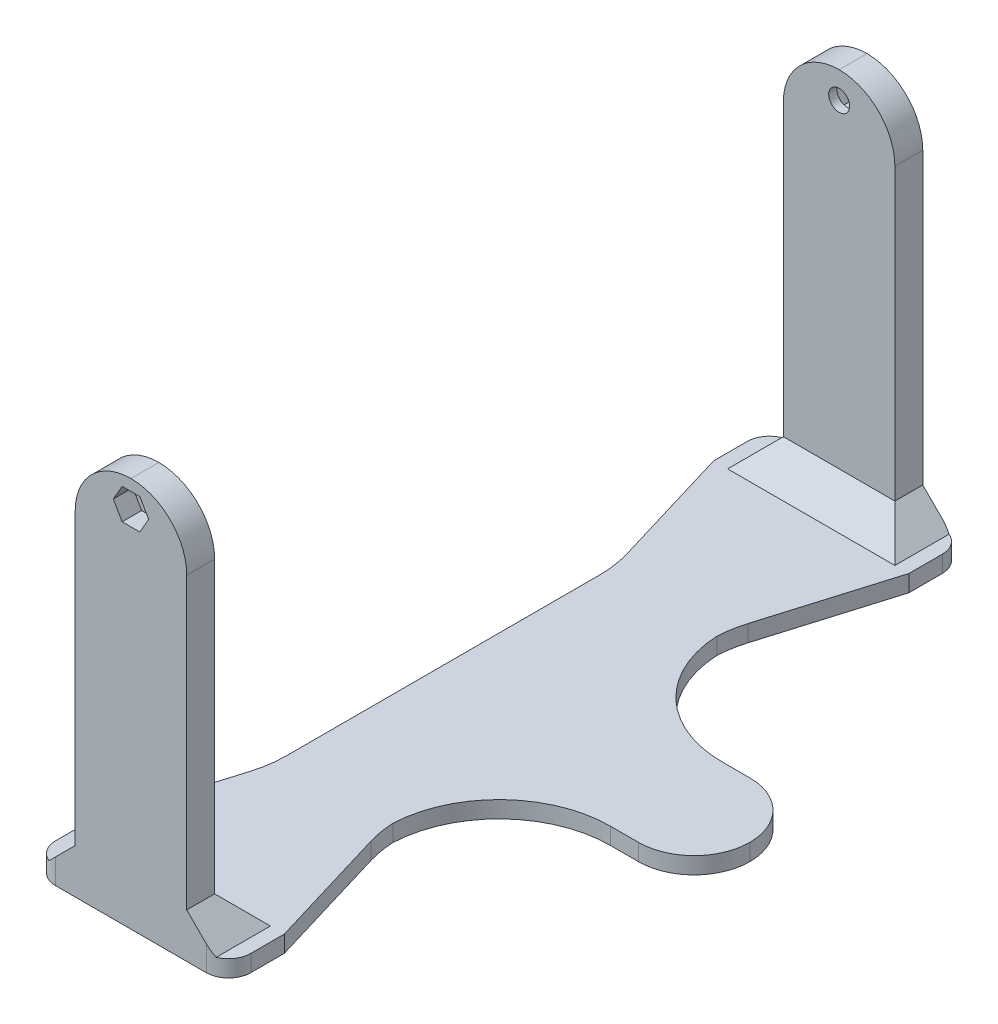
SolidWorks part; units mm, degrees
ref_plane "Front Plane" through (0, 0, 0) normal (0, 0, 1) x (1, 0, 0)
ref_plane "Top Plane" through (0, 0, 0) normal (0, 1, 0) x (1, 0, 0)
ref_plane "Right Plane" through (0, 0, 0) normal (1, 0, 0) x (0, 0, -1)
sketch "Sketch1" plane through (0, 0, 0) normal (0, 1, 0) x (1, 0, 0)
  line L1 (-10, -66) -> (10, -66)
  line L2 (-10, -66) -> (-10, 66)
  line L3 (-10, 66) -> (10, 66)
  line L4 (10, -66) -> (10, 66)
  line L5 (-10, -66) -> (10, 66) construction
  line L6 (-10, 66) -> (10, -66) construction
  point P0 (0, 0)
  dimension "D1" = 132
  dimension "D2" = 20
extrude "Boss-Extrude1" add sketch "Sketch1" along normal blind 3
sketch "Sketch2" plane through (0, 3, 0) normal (0, 1, 0) x (1, 0, 0)
  line L0 (10, -66) -> (10, 66) construction
  line L1 (-10, -66) -> (10, -66)
  line L2 (-10, -66) -> (-10, -61)
  line L3 (-10, -61) -> (10, -61)
  line L4 (10, -66) -> (10, -61)
  line L6 (-10, 66) -> (10, 66)
  line L7 (-10, 66) -> (-10, 61)
  line L8 (-10, 61) -> (10, 61)
  line L9 (10, 66) -> (10, 61)
  dimension "D1" = 5
  dimension "D2" = 5
extrude "Boss-Extrude2" add sketch "Sketch2" along normal blind 67
sketch "Sketch4" plane through (0, 0, 66) normal (0, 0, 1) x (1, 0, 0)
  line L0 (-10, 65.2375) -> (10, 65.2375) construction
  line L1 (-10, 70) -> (-10, 0) construction
  line L2 (10, 70) -> (10, 0) construction
  line L3 (-10, 70) -> (10, 70) construction
  circle A0 centre (0, 65.2375) radius 1.875
  dimension "D1" = 3.75
  dimension "D2" = 4.7625
extrude "Cut-Extrude1" cut sketch "Sketch4" against normal through all
fillet "Fillet3" radius 10 4 edges at (10, 70, 63.5) (-10, 70, 63.5) (10, 70, -63.5) (-10, 70, -63.5)
sketch "Sketch6" plane through (0, 0, 66) normal (0, 0, 1) x (1, 0, 0)
  line L1 (3.1754, 65.2375) -> (1.5877, 67.9875)
  line L2 (1.5877, 67.9875) -> (-1.5877, 67.9875)
  line L3 (-1.5877, 67.9875) -> (-3.1754, 65.2375)
  line L4 (-3.1754, 65.2375) -> (-1.5877, 62.4875)
  line L5 (-1.5877, 62.4875) -> (1.5877, 62.4875)
  line L6 (1.5877, 62.4875) -> (3.1754, 65.2375)
  circle A0 centre (0, 65.2375) radius 2.75 construction
  dimension "D1" = 5.5
extrude "Cut-Extrude2" cut sketch "Sketch6" against normal blind 3.5
sketch "Sketch7" plane through (0, 0, -66) normal (0, 0, -1) x (-1, 0, 0)
  line L1 (3.1754, 65.2375) -> (1.5877, 67.9875)
  line L2 (1.5877, 67.9875) -> (-1.5877, 67.9875)
  line L3 (-1.5877, 67.9875) -> (-3.1754, 65.2375)
  line L4 (-3.1754, 65.2375) -> (-1.5877, 62.4875)
  line L5 (-1.5877, 62.4875) -> (1.5877, 62.4875)
  line L6 (1.5877, 62.4875) -> (3.1754, 65.2375)
  circle A0 centre (0, 65.2375) radius 2.75 construction
  dimension "D1" = 5.5
extrude "Cut-Extrude3" cut sketch "Sketch7" against normal blind 3.5
sketch "Sketch8" plane through (0, 0, 0) normal (0, -1, 0) x (1, 0, 0)
  line L0 (0, 0) -> (0, 50000) construction
  line L1 (-10, 66) -> (10, 66) construction
  line L2 (17.5, -56) -> (-17.5, -56) construction
  line L3 (17.5, -56) -> (17.5, -66)
  line L4 (17.5, -66) -> (-17.5, -66)
  line L5 (-17.5, -56) -> (-17.5, -66)
  line L6 (17.5, -56) -> (-17.5, -66) construction
  line L7 (17.5, -66) -> (-17.5, -56) construction
  line L8 (17.5, 56) -> (-17.5, 56) construction
  line L9 (17.5, 56) -> (17.5, 66)
  line L10 (17.5, 66) -> (-17.5, 66)
  line L11 (-17.5, 56) -> (-17.5, 66)
  line L12 (17.5, 56) -> (-17.5, 66) construction
  line L13 (17.5, 66) -> (-17.5, 56) construction
  line L14 (10, -66) -> (-10, -66) construction
  line L15 (-17.5, -56) -> (-10, -31)
  line L16 (-10, -66) -> (-10, 66) construction
  line L17 (-10, -31) -> (10, -31)
  line L18 (10, 66) -> (10, -66) construction
  line L19 (10, -31) -> (17.5, -56)
  line L20 (17.5, 56) -> (10, 31)
  line L21 (10, 31) -> (-10, 31)
  line L22 (-10, 31) -> (-17.5, 56)
  line L23 (0, 0) -> (50000, 0) construction
  line L25 (45, 10) -> (0, 10)
  line L26 (45, 10) -> (45, -10)
  line L27 (45, -10) -> (0, -10)
  line L28 (0, 10) -> (0, -10)
  line L29 (45, 10) -> (0, -10) construction
  line L30 (45, -10) -> (0, 10) construction
  point P3 (0, -61)
  point P8 (0, 61)
  point P27 (22.5, 0)
  dimension "D1" = 25
  dimension "D2" = 25
  dimension "D3" = 10
  dimension "D4" = 35
  dimension "D5" = 45
  dimension "D6" = 20
extrude "Boss-Extrude3" add sketch "Sketch8" against normal up to surface (3 mm away) up to face at (0, 3, 0)
chamfer "Chamfer1" distance 5 angle 45 6 edges at (10, 3, -63.5) (-10, 3, -63.5) (10, 3, 63.5) (-10, 3, 63.5) (0, 3, 61) (0, 3, -61)
fillet "Fillet4" radius 10 2 edges at (45, 1.5, -10) (45, 1.5, 10)
fillet "Fillet5" radius 4 4 edges at (17.5, 1.5, -66) (-17.5, 1.5, -66) (-17.5, 1.5, 66) (17.5, 1.5, 66)
fillet "Fillet6" radius 20 6 edges at (-10, 1.5, -31) (-10, 1.5, 31) (10, 1.5, 31) (10, 1.5, -31) (10, 1.5, -10) (10, 1.5, 10)
